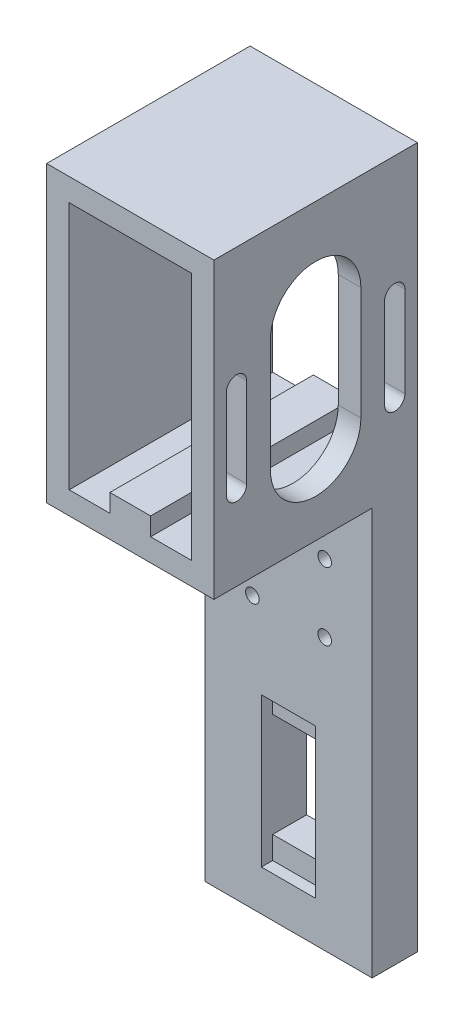
SolidWorks part; units mm, degrees
ref_plane "Plan de face" through (0, 0, 0) normal (0, 0, 1) x (1, 0, 0)
ref_plane "Plan de dessus" through (0, 0, 0) normal (0, 1, 0) x (1, 0, 0)
ref_plane "Plan de droite" through (0, 0, 0) normal (1, 0, 0) x (0, 0, -1)
sketch "Esquisse1" plane through (0, 0, 0) normal (0, 0, 1) x (1, 0, 0)
  line L0 (-40.1057, 31.5871) -> (-35.1057, 31.5871)
  line L2 (-40.1057, 31.5871) -> (-40.1057, -28.4129)
  line L3 (-40.1057, -28.4129) -> (-3.1057, -28.4129)
  line L4 (-3.1057, 31.5871) -> (-3.1057, -28.4129)
  line L5 (-35.1057, 31.5871) -> (-35.1057, -23.4129)
  line L6 (-35.1057, -23.4129) -> (-26.1057, -23.4129)
  line L7 (-26.1057, -23.4129) -> (-26.1057, -19.4129)
  line L8 (-26.1057, -19.4129) -> (-17.1057, -19.4129)
  line L9 (-17.1057, -19.4129) -> (-17.1057, -23.4129)
  line L10 (-17.1057, -23.4129) -> (-8.1057, -23.4129)
  line L11 (-8.1057, -23.4129) -> (-8.1057, 31.5871)
  line L12 (-8.1057, 31.5871) -> (-3.1057, 31.5871)
  dimension "D1" = 37
  dimension "D2" = 60
  dimension "D3" = 5
  dimension "D4" = 5
  dimension "D5" = 9
  dimension "D6" = 9
  dimension "D7" = 5
  dimension "D8" = 4
  dimension "D9" = 4
  dimension "D10" = 9
  dimension "D11" = 60
extrude "Boss.-Extru.1" add sketch "Esquisse1" along normal blind 45
sketch "Esquisse2" plane through (-3.1057, 0, 0) normal (1, 0, 0) x (0, 0, -1)
  line L0 (-22.5, 31.5871) -> (-22.5, -28.4129) construction
  line L1 (-45, 31.5871) -> (0, 31.5871) construction
  line L2 (-45, -28.4129) -> (0, -28.4129) construction
  line L3 (-22.5, 15.0871) -> (-22.5, -9.9129) construction
  line L4 (-12.5, 15.0871) -> (-12.5, -9.9129)
  line L5 (-32.5, 15.0871) -> (-32.5, -9.9129)
  line L6 (-53.101, 2.5871) -> (12.8547, 2.5871) construction
  line L7 (-40, 15.1582) -> (-40, -20.8265) construction
  line L10 (-40, 9.8775) -> (-40, -9.9129) construction
  line L11 (-5, 16.6338) -> (-5, -20.8265) construction
  line L12 (-37.75, 9.8775) -> (-37.75, -9.9129)
  line L13 (-42.25, 9.8775) -> (-42.25, -9.9129)
  line L14 (-37.75, -9.9129) -> (20.4864, -9.9129) construction
  line L15 (20.4864, -9.9129) -> (20.4864, 9.8775) construction
  line L16 (20.4864, 9.8775) -> (-68.9251, 9.8775) construction
  line L17 (-5, 9.8775) -> (-5, -10.1225) construction
  line L18 (-2.75, 9.8775) -> (-2.75, -10.1225)
  line L19 (-7.25, 9.8775) -> (-7.25, -10.1225)
  arc A0 (-12.5, 15.0871) -> (-32.5, 15.0871) centre (-22.5, 15.0871) ccw
  arc A1 (-32.5, -9.9129) -> (-12.5, -9.9129) centre (-22.5, -9.9129) ccw
  arc A4 (-37.75, 9.8775) -> (-42.25, 9.8775) centre (-40, 9.8775) ccw
  arc A5 (-42.25, -9.9129) -> (-37.75, -9.9129) centre (-40, -9.9129) ccw
  arc A6 (-2.75, 9.8775) -> (-7.25, 9.8775) centre (-5, 9.8775) ccw
  arc A7 (-7.25, -10.1225) -> (-2.75, -10.1225) centre (-5, -10.1225) ccw
  point P8 (-22.5, 2.5871)
  point P17 (-40, -0.0177)
  point P33 (-5, -0.1225)
  dimension "D1" = 20
  dimension "D3" = 16.5
  dimension "D2" = 25
  dimension "D4" = 35
  dimension "D5" = 5.25
  dimension "D6" = 4.5
  dimension "D7" = 4.5
  dimension "D8" = 5.25
extrude "Enlèv. mat.-Extru.1" cut sketch "Esquisse2" against normal up to surface (5 mm away) up to face at (-8.1057, 4.0871, 22.5)
sketch "Esquisse4" plane through (0, 31.5871, 0) normal (0, 1, 0) x (1, 0, 0)
  line L0 (-40.1057, -45) -> (-40.1057, 0) construction
  line L1 (-40.1057, 0) -> (-3.1057, 0)
  line L2 (-40.1057, 0) -> (-40.1057, -45)
  line L3 (-40.1057, -45) -> (-3.1057, -45)
  line L4 (-3.1057, 0) -> (-3.1057, -45)
extrude "Boss.-Extru.2" add sketch "Esquisse4" along normal blind 5
sketch "Esquisse5" plane through (0, -28.4129, 0) normal (0, -1, 0) x (1, 0, 0)
  line L0 (-3.1057, 45) -> (-3.1057, 0) construction
  line L1 (-40.1057, 0) -> (-3.1057, 0)
  line L2 (-40.1057, 0) -> (-40.1057, 10)
  line L3 (-40.1057, 10) -> (-3.1057, 10)
  line L4 (-3.1057, 0) -> (-3.1057, 10)
  dimension "D1" = 10
extrude "Boss.-Extru.3" add sketch "Esquisse5" along normal blind 90
sketch "Esquisse6" plane through (-40.1057, 0, 0) normal (-1, 0, 0) x (0, 0, 1)
  line L0 (45, -23.4129) -> (0, -23.4129) construction
  line L1 (45, 36.5871) -> (45, -28.4129) construction
  line L2 (0, 36.5871) -> (0, -118.4129) construction
  line L3 (45, -28.4129) -> (10, -28.4129) construction
  line L4 (15, -23.4129) -> (15, 3.3301) construction
  circle A0 centre (15, -18.4129) radius 1
  circle A1 centre (15, -8.9129) radius 1
  dimension "D2" = 2
  dimension "D5" = 2
  dimension "D1" = 5
  dimension "D3" = 5
  dimension "D4" = 9.5
  dimension "D6" = 15
extrude "Enlèv. mat.-Extru.2" cut sketch "Esquisse6" against normal blind 10
chamfer "Chanfrein2" distance 1 angle 45 2 edges at (-35.1057, -19.4129, 15) (-35.1057, -9.9129, 15)
sketch "Esquisse7" plane through (0, 0, 10) normal (0, 0, 1) x (1, 0, 0)
  line L0 (-21.6057, -28.4129) -> (-21.6057, -118.4129) construction
  line L1 (-3.1057, -28.4129) -> (-40.1057, -28.4129) construction
  line L2 (-3.1057, -118.4129) -> (-40.1057, -118.4129) construction
  line L3 (-27.6057, -104.4129) -> (-15.6057, -104.4129)
  line L4 (-40.1057, -118.4129) -> (-40.1057, -28.4129) construction
  line L5 (-40.1057, -98.4129) -> (-3.1057, -98.4129) construction
  line L6 (-3.1057, -118.4129) -> (-3.1057, -28.4129) construction
  line L7 (-15.6057, -104.4129) -> (-15.6057, -81.4129)
  line L8 (-15.6057, -81.4129) -> (-27.6057, -81.4129)
  line L9 (-27.6057, -81.4129) -> (-27.6057, -104.4129)
  point P15 (-21.6057, -104.4129)
  dimension "D1" = 70
  dimension "D2" = 12
  dimension "D3" = 23
  dimension "D4" = 6
extrude "Enlèv. mat.-Extru.3" cut sketch "Esquisse7" against normal blind 10
sketch "Esquisse8" plane through (0, 0, 10) normal (0, 0, 1) x (1, 0, 0)
  line L1 (-27.6057, -81.4129) -> (-15.6057, -81.4129)
  line L2 (-27.6057, -81.4129) -> (-27.6057, -76.4129)
  line L3 (-27.6057, -76.4129) -> (-15.6057, -76.4129)
  line L4 (-15.6057, -81.4129) -> (-15.6057, -76.4129)
  line L5 (-27.6057, -104.4129) -> (-15.6057, -104.4129)
  line L6 (-27.6057, -104.4129) -> (-27.6057, -109.4129)
  line L7 (-27.6057, -109.4129) -> (-15.6057, -109.4129)
  line L8 (-15.6057, -104.4129) -> (-15.6057, -109.4129)
  dimension "D1" = 12
  dimension "D2" = 12
  dimension "D3" = 5
  dimension "D4" = 5
extrude "Enlèv. mat.-Extru.4" cut sketch "Esquisse8" against normal blind 2.5
sketch "Esquisse10" plane through (0, 0, 10) normal (0, 0, 1) x (1, 0, 0)
  line L0 (-40.1057, -43.4129) -> (-3.1057, -43.4129) construction
  line L1 (-40.1057, -118.4129) -> (-40.1057, -28.4129) construction
  line L2 (-3.1057, -118.4129) -> (-3.1057, -28.4129) construction
  line L3 (-29.6057, -43.4129) -> (-29.6057, -58.4129) construction
  line L4 (-40.1057, -58.4129) -> (-3.1057, -58.4129) construction
  line L5 (-13.6057, -43.4129) -> (-13.6057, -58.4129) construction
  line L6 (-3.1057, -28.4129) -> (-40.1057, -28.4129) construction
  circle A0 centre (-29.6057, -43.4129) radius 1.5
  circle A1 centre (-29.6057, -58.4129) radius 1.5
  circle A2 centre (-13.6057, -58.4129) radius 1.5
  circle A3 centre (-13.6057, -43.4129) radius 1.5
  dimension "D1" = 3
  dimension "D2" = 3
  dimension "D3" = 3
  dimension "D4" = 3
  dimension "D5" = 16
  dimension "D6" = 10.5
  dimension "D7" = 10.5
  dimension "D8" = 15
  dimension "D9" = 15
extrude "Enlèv. mat.-Extru.5" cut sketch "Esquisse10" against normal blind 10
